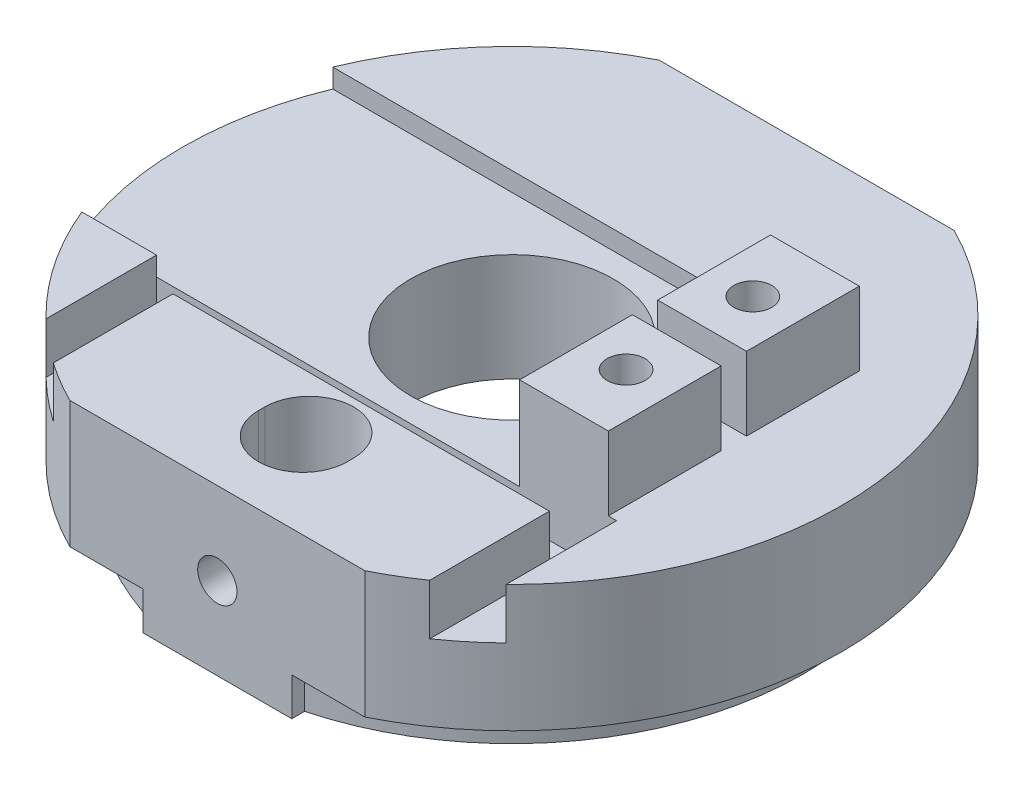
SolidWorks part; units mm, degrees
ref_plane "Front Plane" through (0, 0, 0) normal (0, 0, 1) x (1, 0, 0)
ref_plane "Top Plane" through (0, 0, 0) normal (0, 1, 0) x (1, 0, 0)
ref_plane "Right Plane" through (0, 0, 0) normal (1, 0, 0) x (0, 0, -1)
sketch "Sketch1" plane through (0, 0, 0) normal (0, 1, 0) x (1, 0, 0)
  line L0 (0, -16) -> (0, -16.5) construction
  line L5 (3.5, -16) -> (3.5, -16.5)
  line L6 (-3.5, -16) -> (-3.5, -16.5)
  line L7 (0, -12.5) -> (0, -8) construction
  line L8 (0, 26) -> (0, 23.0025) construction
  line L9 (-17.5, -26) -> (17.5, -26)
  line L10 (-17.5, -26) -> (-17.5, -23.25)
  line L11 (-17.5, -23.25) -> (17.5, -23.25)
  line L12 (17.5, -26) -> (17.5, -23.25)
  line L13 (5.8745, -23.25) -> (-5.8745, -23.25)
  line L14 (5.8745, -23.25) -> (5.8745, -22.2397)
  line L15 (5.8745, -22.2397) -> (-5.8745, -22.2397)
  line L16 (-5.8745, -23.25) -> (-5.8745, -22.2397)
  line L17 (0, 21.0025) -> (0, 23.0025) construction
  line L18 (17.5, 26) -> (-17.5, 26)
  line L19 (17.5, 26) -> (17.5, 23.25)
  line L20 (17.5, 23.25) -> (-17.5, 23.25)
  line L21 (-17.5, 26) -> (-17.5, 23.25)
  circle A0 centre (0, 0) radius 8
  circle A1 centre (0, 0) radius 26
  circle A2 centre (0, 0) radius 23.0025
  circle A3 centre (0, 0) radius 21.0025
  arc A4 (3.5, -16) -> (-3.5, -16) centre (0, -16) ccw
  arc A5 (-3.5, -16.5) -> (3.5, -16.5) centre (0, -16.5) ccw
  circle A6 centre (0, 0) radius 20.75 construction
  circle A7 centre (0, 0) radius 14.5 construction
  point P12 (0, -16.25)
  point P17 (0, -12.5)
  point P18 (0, -20)
  point P23 (0, -26)
  point P24 (0, -22.2397)
  dimension "D1" = 16
  dimension "D2" = 52
  dimension "D3" = 46.005
  dimension "D4" = 2
  dimension "D5" = 3.5
  dimension "D8" = 41.5
  dimension "D9" = 29
  dimension "D6" = 7.5
  dimension "D7" = 4.5
  dimension "D10" = 35
  dimension "D11" = 23.25
  dimension "D12" = 11.749
extrude "Boss-Extrude1" add sketch "Sketch1" along normal blind 10 contours A2 L9 A1 | L9 A2 A3 | A3 A5 L6 A4 L5 A0 | L15 A2 | A2 L16 L11 region at (-25.3024, 0, 0) region at (-5.7566, 0, 22.7449) region at (-13.6417, 0, -17.713) region at (0, 0, 22.5453) region at (-20.4085, 0, 0)
extrude "Boss-Extrude2" add sketch "Sketch1<3>" against normal blind 3 contours L9 A2 A3 | A2 L13 L14 | A2 L15 region at (-5.7566, 0, 22.7449) region at (-13.6417, 0, -17.713) region at (0, 0, 22.5453)
sketch "Sketch1<3>" plane through (0, 0, 0) normal (0, 1, 0) x (1, 0, 0) same geometry as "Sketch1"
sketch "Sketch2" plane through (0, 10, 0) normal (0, 1, 0) x (1, 0, 0)
  line L0 (0, -9.9) -> (0, -12.5) construction
  line L5 (-18.15, -23.25) -> (18.15, -23.25)
  line L6 (-18.15, -23.25) -> (-18.15, -9.9)
  line L7 (-18.15, -9.9) -> (18.15, -9.9)
  line L8 (18.15, -23.25) -> (18.15, -9.9)
  line L10 (-14.85, -23.25) -> (-14.85, -11.9)
  line L11 (-14.85, -11.9) -> (14.85, -11.9)
  line L12 (14.85, -11.9) -> (14.85, -23.25)
  line L13 (-14.85, -11.9) -> (-18.15, -11.9) construction
  line L14 (14.85, -11.9) -> (18.15, -11.9) construction
  line L15 (14.85, -11.9) -> (14.85, -9.9) construction
  line L16 (-11.6378, -23.25) -> (11.6378, -23.25) construction
  line L17 (24.0414, -9.9) -> (-24.0414, -9.9) construction
  arc A0 (3.5, -16) -> (-3.5, -16) centre (0, -16) ccw construction
  arc A1 (11.6378, -23.25) -> (11.6378, 23.25) centre (0, 0) ccw construction
  arc A2 (-11.6378, 23.25) -> (-11.6378, -23.25) centre (0, 0) ccw construction
  point P3 (0, -11.9)
  point P10 (-16.5, -11.9)
  point P21 (16.5, -11.9)
  point P22 (14.85, -10.9)
  dimension "D1" = 3.3
  dimension "D2" = 2
  dimension "D3" = 33
  dimension "D4" = 12.35
  dimension "D5" = 9.9
extrude "Cut-Extrude1" cut sketch "Sketch2" against normal blind 4 contours L11 L12 L8 L7 L6 L10 region at (-17.7632, 10, 16.575)
sketch "Sketch3" plane through (0, 10, 0) normal (0, 1, 0) x (1, 0, 0)
  line L1 (-26, 9.9) -> (10.5, 9.9)
  line L2 (-26, 9.9) -> (-26, -9.9)
  line L3 (-26, -9.9) -> (10.5, -9.9)
  line L4 (10.5, 9.9) -> (10.5, -9.9)
  arc A0 (18.15, -18.6166) -> (11.6378, 23.25) centre (0, 0) ccw construction
  point P4 (10.5, 0)
  dimension "D1" = 19.8
  dimension "D2" = 10.5
extrude "Cut-Extrude2" cut sketch "Sketch3" against normal blind 1.5
sketch "Sketch4" plane through (0, 10, 0) normal (0, 1, 0) x (1, 0, 0)
  line L0 (14, 5) -> (14, -5) construction
  line L1 (10.5, 9.9) -> (17.5, 9.9)
  line L2 (10.5, 9.9) -> (10.5, 1)
  line L3 (10.5, 1) -> (17.5, 1)
  line L4 (17.5, 9.9) -> (17.5, 1)
  line L5 (10.5, -9.9) -> (17.5, -9.9)
  line L6 (10.5, -9.9) -> (10.5, -1)
  line L7 (10.5, -1) -> (17.5, -1)
  line L8 (17.5, -9.9) -> (17.5, -1)
  line L9 (10.5, -9.9) -> (10.5, 9.9) construction
  line L10 (10.5, -9.9) -> (10.5, 9.9) construction
  line L11 (-24.0414, -9.9) -> (-18.15, -9.9) construction
  circle A0 centre (14, 5) radius 1.5
  circle A1 centre (14, -5) radius 1.5
  point P14 (14, 0)
  point P16 (14, -9.9)
  point P20 (10.5, 0)
  dimension "D2" = 10
  dimension "D3" = 3
  dimension "D1" = 2
  dimension "D4" = 3.5
extrude "Boss-Extrude3" add sketch "Sketch4" along normal blind 5.8
sketch "Sketch5" plane through (0, 0, 23.25) normal (0, 0, 1) x (1, 0, 0)
  line L0 (18.15, 6) -> (14.85, 6) construction
  circle A0 centre (0, 3.5) radius 1.55
  dimension "D1" = 3.1
  dimension "D2" = 2.5
extrude "Cut-Extrude3" cut sketch "Sketch5" against normal blind 6
sketch "Sketch6" plane through (0, 0, 0) normal (0, -1, 0) x (1, 0, 0)
  line L0 (5.8745, -23.25) -> (5.8745, -22.2397)
  line L1 (11.6378, -23.25) -> (-11.6378, -23.25) construction
  line L2 (-5.8745, -23.25) -> (-5.8745, -22.2397)
  line L3 (5.8745, -23.25) -> (-5.8745, -23.25)
  line L4 (-5.8745, 23.25) -> (5.8745, 23.25) construction
  arc A0 (-5.8745, 22.2397) -> (5.8745, 22.2397) centre (0, 0) ccw construction
  arc A1 (-5.8745, 22.2397) -> (5.8745, 22.2397) centre (0, 0) ccw
  point P9 (5.7142, -22.2789)
  line M7 (-11.6378, -23.25) -> (11.6378, -23.25)
  arc M11 (5.8745, 22.2397) -> (-5.8745, 22.2397) centre (0, 0) cw
extrude "Boss-Extrude4" add sketch "Sketch6" along normal up to surface (3 mm away) contours L2 L0 M7 M11 region at (0, 0, -23.1321) up to face at (0, -3, 21.0025)
